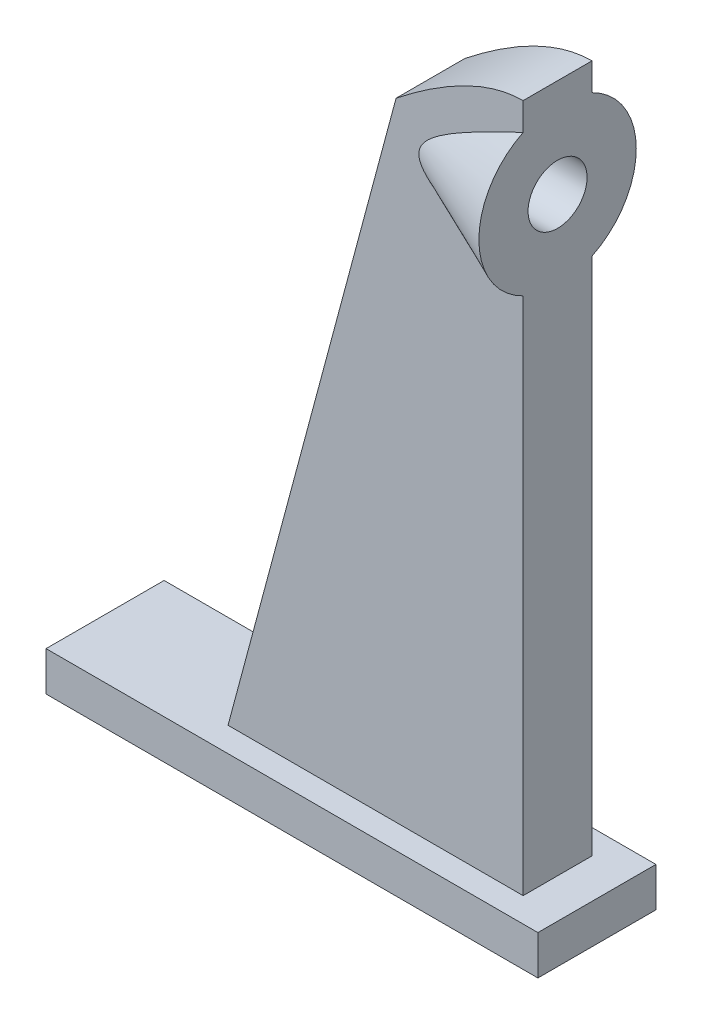
SolidWorks part; units mm, degrees
material "AISI 316 Annealed Stainless Steel Bar (SS)"
ref_plane "Front Plane" through (0, 0, 0) normal (0, 0, 1) x (1, 0, 0)
ref_plane "Top Plane" through (0, 0, 0) normal (0, 1, 0) x (1, 0, 0)
ref_plane "Right Plane" through (0, 0, 0) normal (1, 0, 0) x (0, 0, -1)
sketch "Sketch1" plane through (0, 0, 0) normal (0, 1, 0) x (1, 0, 0)
  line L1 (-125, -30) -> (125, -30)
  line L2 (-125, -30) -> (-125, 30)
  line L3 (-125, 30) -> (125, 30)
  line L4 (125, -30) -> (125, 30)
  line L5 (-125, -30) -> (125, 30) construction
  line L6 (-125, 30) -> (125, -30) construction
  point P0 (0, 0)
  dimension "D1" = 250
  dimension "D2" = 60
extrude "Boss-Extrude1" add sketch "Sketch1" along normal blind 20
sketch "Sketch3" plane through (0, 0, 0) normal (0, 0, 1) x (1, 0, 0)
  line L0 (105, 20) -> (-45, 20)
  line L1 (-125, 20) -> (125, 20) construction
  line L2 (105, 20) -> (105, 370)
  line L3 (-45, 20) -> (40.4103, 338.7555)
  line L4 (167.5359, 370) -> (42.4641, 370) construction
  spline S0 degree 2 poles (40.4103, 338.7555) (80, 370) (105, 370) knots 0 0 0 1 1 1
  dimension "D4" = 105
  dimension "D5" = 50
  dimension "D1" = 150
  dimension "D2" = 350
  dimension "D3" = 330
  dimension "D6" = 75
extrude "Boss-Extrude3" add sketch "Sketch3" along normal blind 17.5 and the other way blind 17.5
sketch "Sketch4" plane through (105, 0, 0) normal (1, 0, 0) x (0, 0, -1)
  line L0 (17.5, 20) -> (-17.5, 20) construction
  circle A0 centre (0, 320) radius 15
  circle A1 centre (0, 320) radius 40
  point P4 (0, 20)
  dimension "D1" = 30
  dimension "D3" = 80
  dimension "D2" = 300
extrude "Boss-Extrude5" add sketch "Sketch4" against normal blind 80 draft 23 contours A1
extrude "Cut-Extrude3" cut sketch "Sketch4<4>" against normal blind 168 contours A0
sketch "Sketch4<4>" plane through (105, 0, 0) normal (1, 0, 0) x (0, 0, -1) same geometry as "Sketch4"
